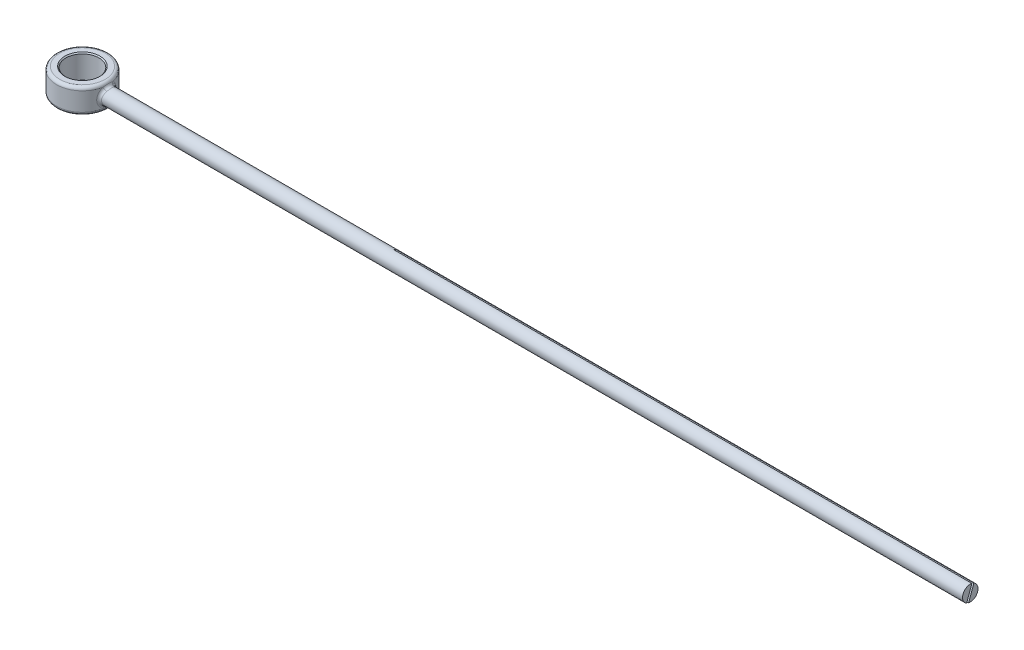
SolidWorks part; units mm, degrees
ref_plane "Piano frontale" through (0, 0, 0) normal (0, 0, 1) x (1, 0, 0)
ref_plane "Piano superiore" through (0, 0, 0) normal (0, 1, 0) x (1, 0, 0)
ref_plane "Piano destro" through (0, 0, 0) normal (1, 0, 0) x (0, 0, -1)
sketch "Schizzo1" plane through (0, 0, 0) normal (0, 1, 0) x (1, 0, 0)
  circle A1 centre (0, 0) radius 25
  dimension "D1" = 50
extrude "Estrusione1" add sketch "Schizzo1" along normal mid plane 24
sketch "Schizzo2" plane through (0, 0, 0) normal (1, 0, 0) x (0, 0, -1)
  circle A0 centre (0, 0) radius 7.5
  dimension "D1" = 15
extrude "Estrusione2" add sketch "Schizzo2" along normal blind 860
sketch "Schizzo3" plane through (0, 12, 0) normal (0, 1, 0) x (1, 0, 0)
  circle A0 centre (0, 0) radius 16
  dimension "D1" = 32
extrude "Estrusione3" cut sketch "Schizzo3" against normal through all
fillet "Raccordo1" radius 3 2 edges at (0, -12, 25) (0, 12, 25)
fillet "Raccordo2" radius 3 1 edges at (23.8873, 1.3617, -7.3753)
chamfer "Smusso1" distance 1 angle 45 2 edges at (0, -12, 16) (0, 12, 16)
sketch "Schizzo5" plane through (860, 0, 0) normal (1, 0, 0) x (0, 0, -1)
  line L0 (-7.2274, -16.9334) -> (5.3481, 17.6175)
  line L1 (-7.2274, -16.9334) -> (-5.3481, -17.6175)
  line L2 (5.3481, 17.6175) -> (7.2274, 16.9334)
  line L3 (-5.3481, -17.6175) -> (7.2274, 16.9334)
  line L4 (0, 0) -> (0, 27.5018) construction
  line L5 (-6.2877, -17.2754) -> (6.2877, 17.2754) construction
  point P9 (0, 0)
  dimension "D1" = 20
  dimension "D2" = 2
extrude "Estrusione4" cut sketch "Schizzo5" against normal blind 560
